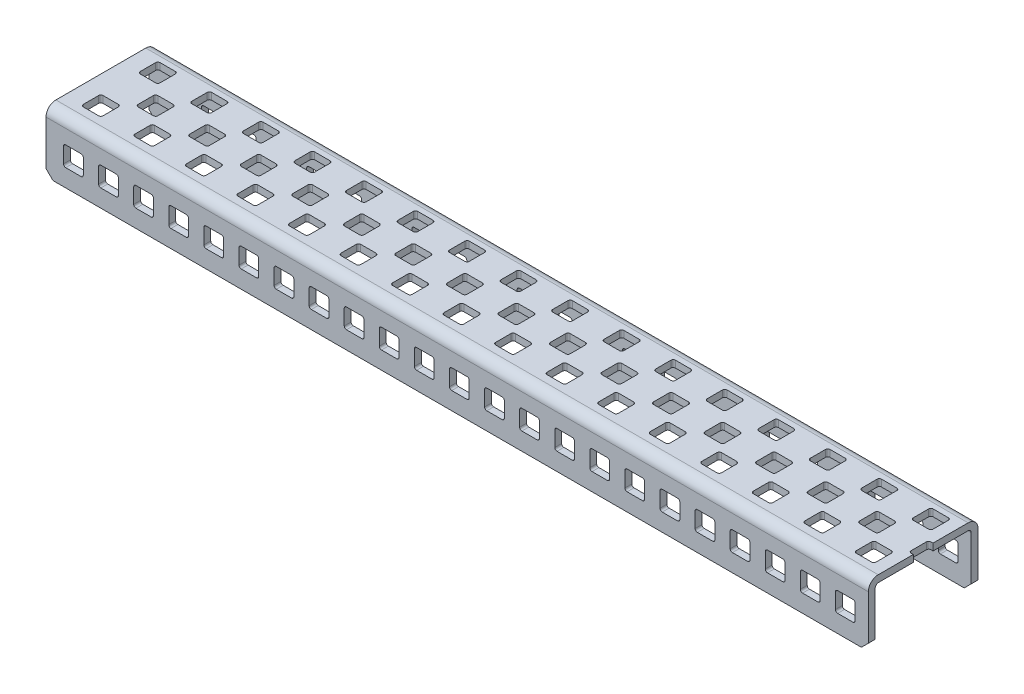
SolidWorks part; units mm, degrees
ref_plane "Front Plane" through (0, 0, 0) normal (0, 0, 1) x (1, 0, 0)
ref_plane "Top Plane" through (0, 0, 0) normal (0, 1, 0) x (1, 0, 0)
ref_plane "Right Plane" through (0, 0, 0) normal (1, 0, 0) x (0, 0, -1)
sketch "Sketch1" plane through (0, 0, 0) normal (1, 0, 0) x (0, 0, -1)
  line L0 (0, 0) -> (0, 11.938)
  line L1 (2.286, 14.224) -> (23.114, 14.224)
  line L2 (25.4, 11.938) -> (25.4, 0)
  line L3 (25.4, 0) -> (23.8125, 0)
  line L4 (23.8125, 0) -> (23.8125, 11.8745)
  line L5 (23.0505, 12.6365) -> (2.3495, 12.6365)
  line L6 (1.5875, 11.8745) -> (1.5875, 0)
  line L7 (1.5875, 0) -> (0, 0)
  arc A0 (23.8125, 11.8745) -> (23.0505, 12.6365) centre (23.0505, 11.8745) ccw
  arc A1 (2.3495, 12.6365) -> (1.5875, 11.8745) centre (2.3495, 11.8745) ccw
  arc A2 (23.114, 14.224) -> (25.4, 11.938) centre (23.114, 11.938) cw
  arc A3 (0, 11.938) -> (2.286, 14.224) centre (2.286, 11.938) cw
  dimension "D6" = 0.762
  dimension "D7" = 2.286
  dimension "D1" = 1.5875
  dimension "D2" = 1.5875
  dimension "D3" = 1.5875
  dimension "D4" = 22.225
  dimension "D5" = 14.224
extrude "Boss-Extrude2" add sketch "Sketch1" along normal blind 190.5
sketch "Sketch2" plane through (0, 0, 0) normal (0, 0, 1) x (1, 0, 0)
  line L0 (190.5, 0) -> (0, 0) construction
  line L1 (4.572, 8.636) -> (8.128, 8.636)
  line L2 (4.064, 8.128) -> (4.064, 4.572)
  line L3 (4.572, 4.064) -> (8.128, 4.064)
  line L4 (8.636, 8.128) -> (8.636, 4.572)
  line L5 (0, 11.938) -> (0, 0) construction
  arc A0 (4.064, 4.572) -> (4.572, 4.064) centre (4.572, 4.572) ccw
  arc A1 (8.128, 4.064) -> (8.636, 4.572) centre (8.128, 4.572) ccw
  arc A2 (8.128, 8.636) -> (8.636, 8.128) centre (8.128, 8.128) cw
  arc A3 (4.572, 8.636) -> (4.064, 8.128) centre (4.572, 8.128) ccw
  point P12 (8.636, 4.064)
  point P15 (8.636, 8.636)
  dimension "D5" = 0.508
  dimension "D1" = 4.572
  dimension "D2" = 4.572
  dimension "D3" = 4.064
  dimension "D4" = 4.064
extrude "Cut-Extrude1" cut sketch "Sketch2" against normal through all
pattern_linear "LPattern1" count 39 spacing 8.128 along (1, 0, 0) of "Cut-Extrude1"
sketch "Sketch3" plane through (0, 0, 0) normal (0, 0, 1) x (1, 0, 0)
  line L0 (0, 1.6164) -> (1.6164, 0)
  line L1 (0, 11.938) -> (0, 0) construction
  line L2 (190.5, 0) -> (0, 0) construction
  line L3 (1.6164, 0) -> (0, 0)
  line L4 (0, 0) -> (0, 1.6164)
  dimension "D1" = 2.286
extrude "Cut-Extrude2" cut sketch "Sketch3" against normal through all
sketch "Sketch4" plane through (0, 0, 0) normal (0, 0, 1) x (1, 0, 0)
  line L10 (188.8836, 0) -> (190.5, 1.6164)
  line L11 (190.5, 0) -> (1.6164, 0) construction
  line L12 (190.5, 11.938) -> (190.5, 0) construction
  line L13 (190.5, 1.6164) -> (190.5, 0)
  line L14 (190.5, 0) -> (188.8836, 0)
  dimension "D2" = 2.286
extrude "Cut-Extrude3" cut sketch "Sketch4" against normal through all
sketch "Sketch5" plane through (0, 14.224, 0) normal (0, 1, 0) x (1, 0, 0)
  line L1 (4.572, 4.064) -> (8.128, 4.064)
  line L2 (4.064, 4.572) -> (4.064, 8.128)
  line L3 (4.572, 8.636) -> (8.128, 8.636)
  line L4 (8.636, 4.572) -> (8.636, 8.128)
  line L5 (190.5, 0) -> (0, 0) construction
  line L6 (0, 23.114) -> (0, 2.286) construction
  arc A0 (8.128, 4.064) -> (8.636, 4.572) centre (8.128, 4.572) ccw
  arc A1 (8.128, 8.636) -> (8.636, 8.128) centre (8.128, 8.128) cw
  arc A2 (4.064, 8.128) -> (4.572, 8.636) centre (4.572, 8.128) cw
  arc A3 (4.572, 4.064) -> (4.064, 4.572) centre (4.572, 4.572) cw
  dimension "D3" = 0.508
  dimension "D1" = 4.572
  dimension "D2" = 4.572
  dimension "D4" = 4.064
  dimension "D5" = 4.064
extrude "Cut-Extrude4" cut sketch "Sketch5" against normal through all
pattern_linear "LPattern2" count 2 spacing 13.208 along (0, 0, -1) count 27 spacing 11.938 along (1, 0, 0) of "Cut-Extrude4"
sketch "Sketch6" plane through (0, 14.224, 0) normal (0, 1, 0) x (1, 0, 0)
  line L0 (0, 23.114) -> (0, 2.286) construction
  line L1 (10.922, 14.986) -> (14.478, 14.986)
  line L2 (10.414, 14.478) -> (10.414, 10.922)
  line L3 (10.922, 10.414) -> (14.478, 10.414)
  line L4 (14.986, 14.478) -> (14.986, 10.922)
  line L5 (190.5, 2.286) -> (0, 2.286) construction
  arc A0 (10.414, 10.922) -> (10.922, 10.414) centre (10.922, 10.922) ccw
  arc A1 (14.478, 10.414) -> (14.986, 10.922) centre (14.478, 10.922) ccw
  arc A2 (14.478, 14.986) -> (14.986, 14.478) centre (14.478, 14.478) cw
  arc A3 (10.922, 14.986) -> (10.414, 14.478) centre (10.922, 14.478) ccw
  point P8 (10.414, 12.7)
  point P13 (14.986, 10.414)
  point P16 (14.986, 14.986)
  dimension "D5" = 0.508
  dimension "D1" = 10.414
  dimension "D2" = 8.128
  dimension "D3" = 4.572
  dimension "D4" = 4.572
extrude "Cut-Extrude5" cut sketch "Sketch6" against normal through all
pattern_linear "LPattern3" count 26 spacing 11.938 along (1, 0, 0) of "Cut-Extrude5"
